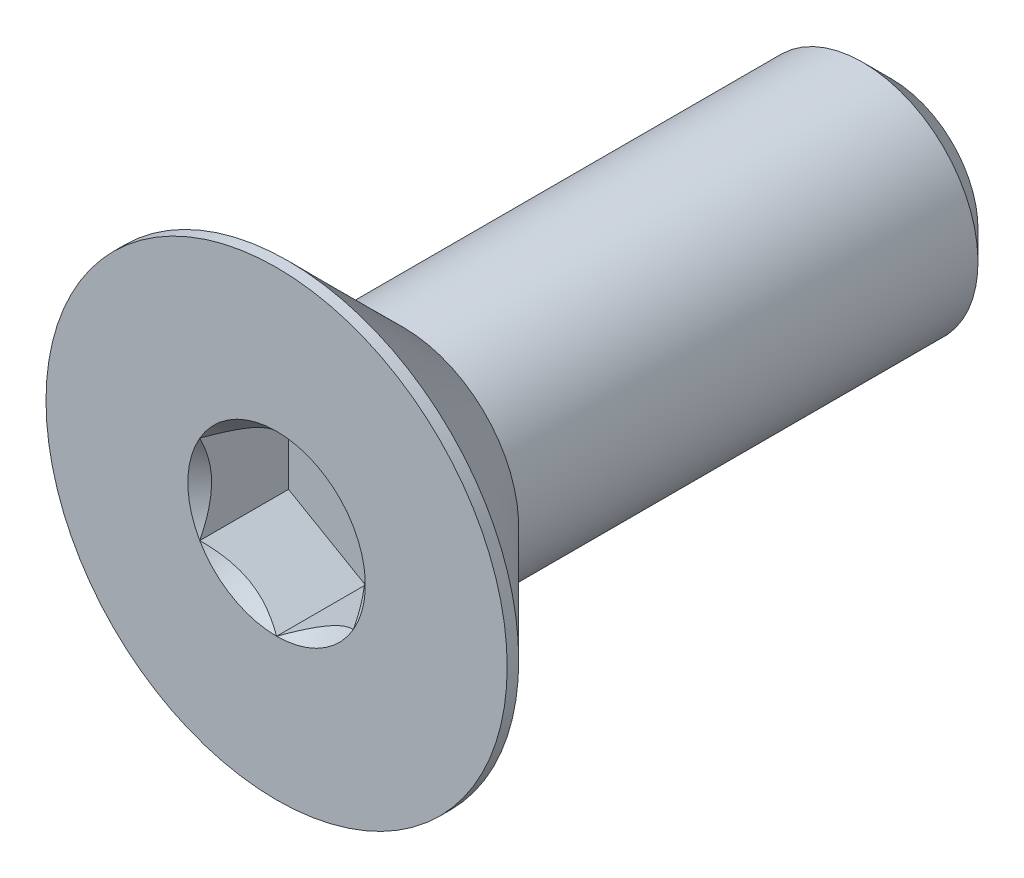
SolidWorks part; units mm, degrees
material "AISI 304"
ref_plane "Front" through (0, 0, 0) normal (0, 0, 1) x (1, 0, 0)
ref_plane "Top" through (0, 0, 0) normal (0, 1, 0) x (1, 0, 0)
ref_plane "Right" through (0, 0, 0) normal (1, 0, 0) x (0, 0, -1)
sketch "Sketch1" plane through (0, 0, 0) normal (1, 0, 0) x (0, 0, -1)
  line L0 (0, 6) -> (0.3, 6) construction
  line L1 (0.3, 6) -> (3.3, 3) construction
  line L2 (0, 3) -> (16, 3)
  line L3 (16, 3) -> (16, 0)
  line L4 (16, 0) -> (0, 0)
  line L5 (0, 0) -> (0, 6) construction
  line L6 (0, 6) -> (0, -6) construction
  line L7 (16, 3) -> (16, -3) construction
  line L8 (0, -6) -> (0.3, -6) construction
  line L9 (0.3, -6) -> (3.3, -3) construction
  line L11 (0, 3) -> (0, 0)
  line L12 (3.3, 3) -> (3.3, 0) construction
revolve "Revolve1" add sketch "Sketch1" angle 360 mid plane about L4
sketch "Sketch3" plane through (0, 0, -16) normal (0, 0, -1) x (-1, 0, 0)
  circle A0 centre (0, 0) radius 3
curve "Helix/Spiral1" pitch 1 height 16 turns 16
sketch "Sketch2" plane through (0, 0, 0) normal (1, 0, 0) x (0, 0, -1)
  line L0 (16, 3) -> (16.875, 3)
  line L1 (16.875, 3) -> (16.5, 2.3505)
  line L2 (16.5, 2.3505) -> (16.375, 2.3505)
  line L3 (16.375, 2.3505) -> (16, 3)
  line L4 (16.1875, 2.6752) -> (16.6875, 2.6752) construction
  dimension "D1" = 60
  dimension "D2" = 0.125
  dimension "D3" = 0.5
chamfer "Chamfer1" distance 0.75 angle 45 1 edges at (0, 3, -16)
sweep "Cut-Sweep1" [suppressed] cut profiles "Sketch2" path "Helix/Spiral1"
sketch "Sketch7" plane through (0, 0, 0) normal (1, 0, 0) x (0, 0, -1)
  line L0 (0, 6) -> (0.3, 6) construction
  line L1 (0.3, 6) -> (3.3, 3) construction
  line L2 (0, 6) -> (0.3, 6)
  line L3 (0.3, 6) -> (3.3, 3)
  line L4 (3.3, 3) -> (3.3, 0) construction
  line L5 (3.3, 3) -> (3.3, 0)
  line L7 (0, 0) -> (0, 6) construction
  line L8 (0, 0) -> (0, 6)
  line L9 (0, 0) -> (3.3, 0)
  line L10 (6.6, 0) -> (-6.6, 0) construction
revolve "Revolve2" add sketch "Sketch7" angle 360 mid plane about L9
ref_plane "Plane1" through (0, 0, -3.3) normal (0, 0, 1) x (1, 0, 0)
sketch "Sketch8" plane through (0, 0, -3.3) normal (0, 0, 1) x (1, 0, 0)
  circle A0 centre (0, 0) radius 3
extrude "Boss-Extrude1" add sketch "Sketch8" against normal through all draft 45
sketch "Sketch5" plane through (0, 0, 0) normal (0, 0, 1) x (1, 0, 0)
  line L1 (2, -1.1547) -> (2, 1.1547)
  line L2 (2, 1.1547) -> (0, 2.3094)
  line L3 (0, 2.3094) -> (-2, 1.1547)
  line L4 (-2, 1.1547) -> (-2, -1.1547)
  line L5 (-2, -1.1547) -> (0, -2.3094)
  line L6 (0, -2.3094) -> (2, -1.1547)
  circle A0 centre (0, 0) radius 2 construction
  dimension "Hex" = 4
extrude "Cut-Extrude2" cut sketch "Sketch5" against normal blind 2.31
sketch "Sketch6" plane through (0, 0, 0) normal (0, 0, 1) x (1, 0, 0)
  circle A0 centre (0, 0) radius 2.3094
extrude "Cut-Extrude3" cut sketch "Sketch6" against normal blind 2.31 draft 45
sketch "Sketch9" [suppressed] plane through (0, 0, -5.5) normal (0, 0, 1) x (1, 0, 0)
  circle A1 centre (0, 0) radius 5
  circle A2 centre (0, 0) radius 5
  point P0 (0, 5)
  dimension "D1" = 0
extrude "Boss-Extrude2" [suppressed] add sketch "Sketch9" against normal offset from surface (18.5 mm away) 26
fillet "Fillet1" [suppressed] radius 0.6
sketch "Sketch10" plane through (0, 0, 0) normal (1, 0, 0) x (0, 0, -1)
  line L0 (16, 3) -> (16, -3) construction
  point P0 (14.5, -3)
  dimension "D1" = 1.5
equation "\"D3@Helix/Spiral1\" = \"Lg@Sketch1\""
equation "\"D2@Sketch2\" = \"D4@Helix/Spiral1\" * .125"
equation "\"D3@Sketch2\" = \"D4@Helix/Spiral1\" * .5"
equation "\"D1@Chamfer1\" = \"D4@Helix/Spiral1\" * .75"
equation "\"D1@Cut-Extrude2\" = \"Head Ht@Sketch1\" * .7"
equation "\"D1@Sketch10\" = \"D4@Helix/Spiral1\" * 1.5"
equation "\"D1@Cut-Extrude3\" = \"D1@Cut-Extrude2\""
equation "\"D1@Fillet1\" = \"Dia@Sketch1\" * .1"
